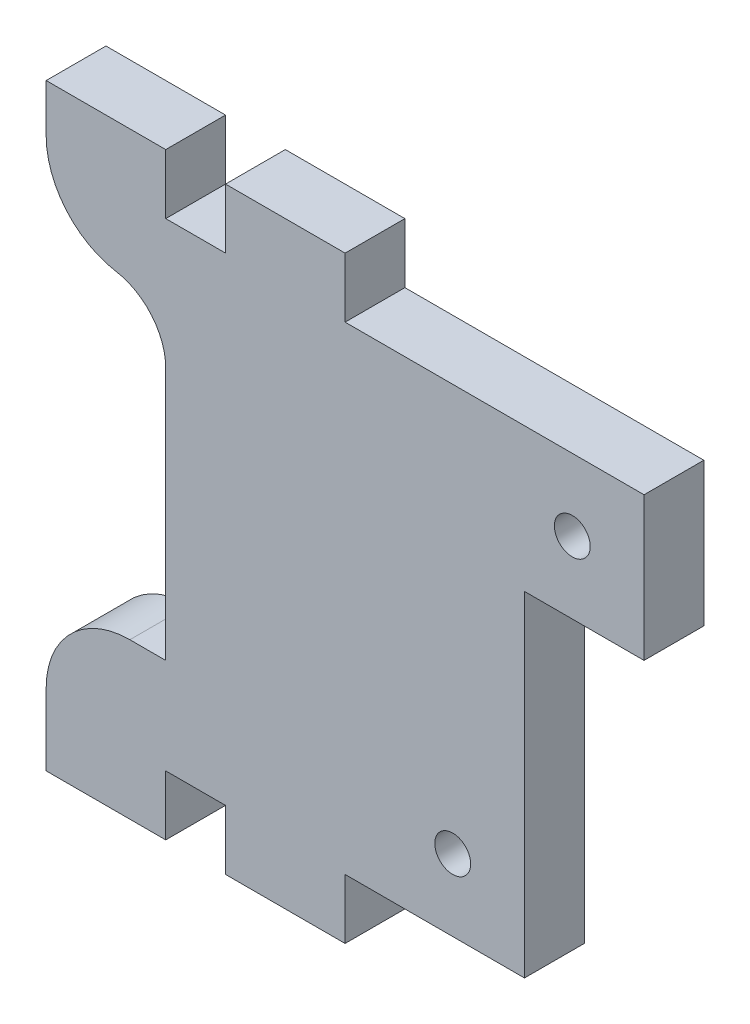
SolidWorks part; units mm, degrees
ref_plane "Plan de face" through (0, 0, 0) normal (0, 0, 1) x (1, 0, 0)
ref_plane "Plan de dessus" through (0, 0, 0) normal (0, 1, 0) x (1, 0, 0)
ref_plane "Plan de droite" through (0, 0, 0) normal (1, 0, 0) x (0, 0, -1)
sketch "Esquisse1" plane through (0, 0, 0) normal (0, 0, 1) x (1, 0, 0)
  line L0 (0, 20) -> (40, 20) construction
  line L1 (10, 0) -> (15, 0)
  line L2 (0, 0) -> (0, 8)
  line L3 (10, 40) -> (15, 40)
  line L4 (50, 28) -> (50, 40)
  line L5 (25, 40) -> (50, 40)
  line L6 (0, 40) -> (0, 45)
  line L7 (0, 45) -> (10, 45)
  line L8 (10, 40) -> (10, 45)
  line L9 (25, 0) -> (40, 0)
  line L10 (15, 40) -> (15, 45)
  line L11 (15, 45) -> (25, 45)
  line L12 (25, 40) -> (25, 45)
  line L13 (25, 0) -> (25, -5)
  line L14 (15, -5) -> (25, -5)
  line L15 (15, 0) -> (15, -5)
  line L16 (10, 0) -> (10, -5)
  line L17 (0, -5) -> (10, -5)
  line L18 (0, 0) -> (0, -5)
  line L19 (0, 34) -> (0, 40)
  line L20 (0, 8) -> (10, 8)
  line L22 (0, 34) -> (10, 34)
  line L23 (10, 8) -> (10, 34)
  line L25 (40, 0) -> (40, 28)
  line L26 (40, 28) -> (50, 28)
  circle A0 centre (44, 34) radius 1.5
  circle A1 centre (34, 6) radius 1.5
  dimension "D9" = 3
  dimension "D11" = 6
  dimension "D1" = 40
  dimension "D2" = 50
  dimension "D3" = 10
  dimension "D4" = 5
  dimension "D5" = 5
  dimension "D6" = 10
  dimension "D7" = 8
  dimension "D8" = 26
  dimension "D10" = 6
  dimension "D12" = 6
  dimension "D13" = 16
  dimension "D14" = 10
  dimension "D15" = 28
extrude "Boss.-Extru.1" add sketch "Esquisse1" along normal blind 5
fillet "Congé1" radius 7 2 edges at (0, 8, 2.5) (0, 34, 2.5)
fillet "Congé2" radius 5 1 edges at (10, 34, 2.5)
